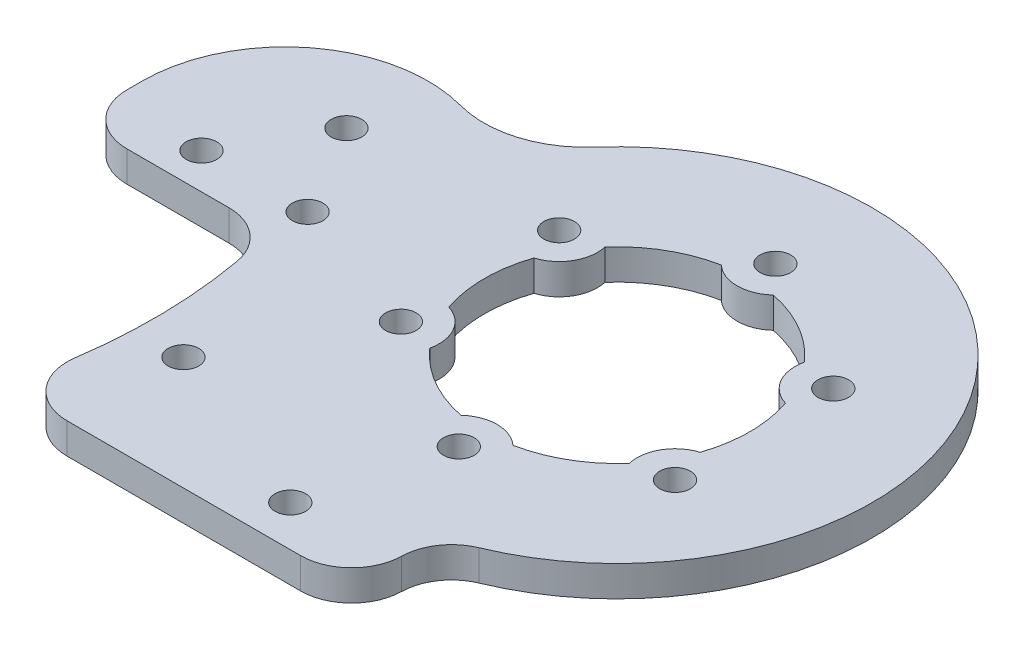
SolidWorks part; units mm, degrees
ref_plane "前视基准面" through (0, 0, 0) normal (0, 0, 1) x (1, 0, 0)
ref_plane "上视基准面" through (0, 0, 0) normal (0, 1, 0) x (1, 0, 0)
ref_plane "右视基准面" through (0, 0, 0) normal (1, 0, 0) x (0, 0, -1)
sketch "草图1" plane through (0, 0, 0) normal (0, 1, 0) x (1, 0, 0)
  line L0 (-46.5, -0.005) -> (-18.5, -0.005) construction
  line L1 (-46.5, -0.005) -> (-46.5, -6.505)
  line L2 (6.5, -24.1402) -> (6.5, -32.5)
  line L3 (0, 0) -> (0, 15.5) construction
  line L4 (-27.3038, -3.005) -> (-3.5, -28.5) construction
  line L5 (-15.4019, -15.7525) -> (-21.0588, -21.4094) construction
  line L6 (6.5, -32.5) -> (6.5, -18.5) construction
  line L7 (6.5, -18.5) -> (0, -18.5) construction
  line L8 (-27.5, -6.505) -> (-27.5, -32.5) construction
  line L9 (-27.5, -6.505) -> (-46.5, -6.505)
  line L10 (0, 0) -> (-9.7664, 8.58) construction
  line L11 (-27.5, -32.5) -> (6.5, -32.5)
  arc A0 (6.5, -24.1402) -> (-22.8516, 10.1393) centre (0, 0) ccw
  arc A1 (-18.5, -0.005) -> (0, -18.5) centre (0, 0) ccw construction
  arc A2 (-22.8516, 10.1393) -> (-46.5, -0.005) centre (-32.5, -0.005) ccw
  circle A3 centre (-32.5, -0.005) radius 6 construction
  circle A4 centre (-32.5, 5.995) radius 1.5
  circle A5 centre (-27.3038, -3.005) radius 1.5
  circle A6 centre (-3.5, -28.5) radius 1.5
  circle A7 centre (-37.6962, -3.005) radius 1.5
  circle A8 centre (0, 0) radius 15.5 construction
  circle A9 centre (-21.0588, -21.4094) radius 1.5
  circle A10 centre (0, 15.5) radius 1.5
  circle A11 centre (13.4234, 7.75) radius 1.5
  circle A12 centre (13.4234, -7.75) radius 1.5
  circle A13 centre (0, -15.5) radius 1.5
  circle A14 centre (-13.4234, -7.75) radius 1.5
  circle A15 centre (-13.4234, 7.75) radius 1.5
  arc A16 (-12.3137, 4.1679) -> (-12.3137, -4.1679) centre (0, 0) ccw
  arc A17 (-2.5473, 12.748) -> (2.5473, 12.748) centre (0, 15.5) ccw
  arc A18 (9.7664, 8.58) -> (12.3137, 4.1679) centre (13.4234, 7.75) ccw
  arc A19 (12.3137, -4.1679) -> (9.7664, -8.58) centre (13.4234, -7.75) ccw
  arc A20 (2.5473, -12.748) -> (-2.5473, -12.748) centre (0, -15.5) ccw
  arc A21 (-9.7664, -8.58) -> (-12.3137, -4.1679) centre (-13.4234, -7.75) ccw
  arc A22 (-12.3137, 4.1679) -> (-9.7664, 8.58) centre (-13.4234, 7.75) ccw
  arc A23 (-2.5473, 12.748) -> (-9.7664, 8.58) centre (0, 0) ccw
  arc A24 (9.7664, 8.58) -> (2.5473, 12.748) centre (0, 0) ccw
  arc A25 (12.3137, -4.1679) -> (12.3137, 4.1679) centre (0, 0) ccw
  arc A26 (2.5473, -12.748) -> (9.7664, -8.58) centre (0, 0) ccw
  arc A27 (-9.7664, -8.58) -> (-2.5473, -12.748) centre (0, 0) ccw
  arc A28 (-27.5, -6.505) -> (-27.5, -32.5) centre (-75.7811, -19.5025) cw
  point P26 (-32.5, -0.005)
  dimension "D3" = 32.5
  dimension "D1" = 14
  dimension "D2" = 18.5
  dimension "D6" = 12
  dimension "D8" = 3
  dimension "D9" = 6.5
  dimension "D12" = 6.5
  dimension "D13" = 3
  dimension "D15" = 50
  dimension "D16" = 31
  dimension "D17" = 3
  dimension "D20" = 13
  dimension "D21" = 6
  dimension "D22" = 3.75
  dimension "D23" = 50
  dimension "D4" = 19
  dimension "D5" = 25.995
  dimension "D10" = 10
  dimension "D11" = 10
  dimension "D14" = 8
  dimension "D19" = 15.5
  dimension "D7" = 3
  dimension "D18" = 6
extrude "凸台-拉伸1" add sketch "草图1" along normal blind 3
fillet "圆角1" radius 5 3 edges at (-46.5, 1.5, 6.505) (-27.5, 1.5, 32.5) (-27.5, 1.5, 6.505)
fillet "圆角2" radius 10 1 edges at (-22.8516, 1.5, -10.1393)
fillet "圆角6" radius 5 1 edges at (6.5, 1.5, 24.1402)
fillet "圆角7" radius 5 1 edges at (6.5, 1.5, 32.5)
